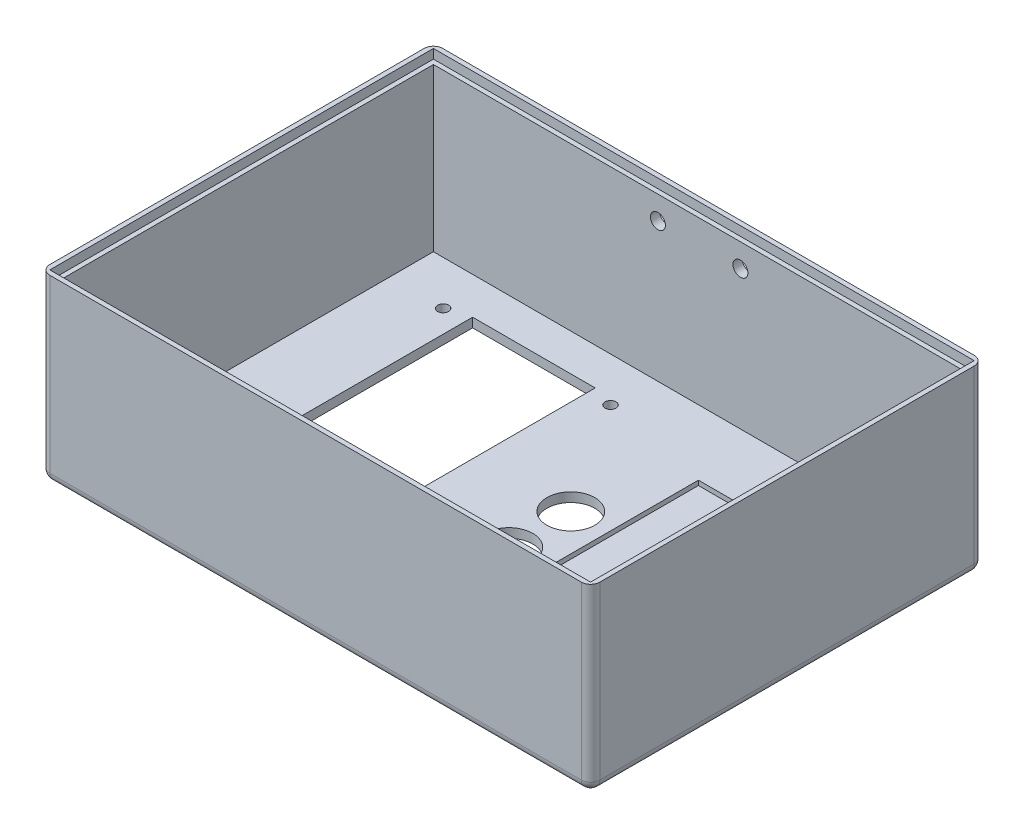
SolidWorks part; units mm, degrees
ref_plane "Front Plane" through (0, 0, 0) normal (0, 0, 1) x (1, 0, 0)
ref_plane "Top Plane" through (0, 0, 0) normal (0, 1, 0) x (1, 0, 0)
ref_plane "Right Plane" through (0, 0, 0) normal (1, 0, 0) x (0, 0, -1)
ref_plane "Plane1" through (0, 58.42, 0) normal (0, 1, 0) x (1, 0, 0)
sketch "Sketch1" plane through (0, 58.42, 0) normal (0, 1, 0) x (1, 0, 0)
  line L0 (-88.9, -63.5) -> (88.9, -63.5)
  line L1 (88.9, -63.5) -> (88.9, 63.5)
  line L2 (88.9, 63.5) -> (-88.9, 63.5)
  line L3 (-88.9, 63.5) -> (-88.9, -63.5)
extrude "Boss-Extrude1" add sketch "Sketch1" against normal blind 58.42
sketch "Sketch2" plane through (0, 58.42, 0) normal (0, 1, 0) x (-1, 0, 0)
  line L0 (87.4, 62) -> (-87.4, 62)
  line L1 (-87.4, 62) -> (-87.4, -62)
  line L2 (-87.4, -62) -> (87.4, -62)
  line L3 (87.4, -62) -> (87.4, 62)
extrude "Cut-Extrude1" cut sketch "Sketch2" against normal blind 3
sketch "Sketch3" plane through (0, 55.42, 0) normal (0, 1, 0) x (-1, 0, 0)
  line L0 (85.9, 60.5) -> (-85.9, 60.5)
  line L1 (-85.9, 60.5) -> (-85.9, -60.5)
  line L2 (-85.9, -60.5) -> (85.9, -60.5)
  line L3 (85.9, -60.5) -> (85.9, 60.5)
extrude "Cut-Extrude2" cut sketch "Sketch3" against normal blind 52.42
sketch "Sketch4" plane through (0, 3, 0) normal (0, 1, 0) x (-1, 0, 0)
  line L0 (21.624, -48.514) -> (61.248, -48.514)
  line L1 (61.248, -48.514) -> (61.248, 48.514)
  line L2 (61.248, 48.514) -> (21.624, 48.514)
  line L3 (21.624, 48.514) -> (21.624, -48.514)
extrude "Cut-Extrude3" cut sketch "Sketch4" against normal through all
sketch "Sketch5" plane through (0, 3, 0) normal (0, 1, 0) x (-1, 0, 0)
  line L0 (-20.8712, 52.0517) -> (-79.2912, 52.0517)
  line L1 (-79.2912, 52.0517) -> (-79.2912, -39.3883)
  line L2 (-79.2912, -39.3883) -> (-20.8712, -39.3883)
  line L3 (-20.8712, -39.3883) -> (-20.8712, 52.0517)
extrude "Cut-Extrude4" cut sketch "Sketch5" against normal blind 1.5
hole_wizard "M13 Clearance Hole1" positions "Sketch7" profile "Sketch6" hole size "M13" standard "ANSI Metric"
sketch "Sketch7" plane through (0, 3, 0) normal (0, 1, 0) x (1, 0, 0)
  point P0 (8.9925, -10.0168)
  point P1 (8.9925, 10.0168)
sketch "Sketch6" plane through (8.9925, 3, 10.0168) normal (1, 0, 0) x (0, 0, 1)
  line L0 (0, 0) -> (0, 3)
  line L1 (0, 3) -> (7.747, 3)
  line L2 (7.747, 3) -> (7.747, 0)
  line L5 (7.747, 0) -> (0, 0)
  line L11 (0, -6.35) -> (0, 107.95) construction
  dimension "Thru Hole Dia." = 15.494
  dimension "Thru Hole Depth" = 3
hole_wizard "M3 Clearance Hole1" positions "Sketch9" profile "Sketch8" hole size "M3" standard "ANSI Metric"
sketch "Sketch9" plane through (0, 3, 0) normal (0, 1, 0) x (1, 0, 0)
  point P0 (-68.487, 46.228)
  point P1 (-68.487, -46.228)
  point P2 (-14.385, -46.228)
  point P3 (-14.385, 46.228)
sketch "Sketch8" plane through (-68.487, 3, -46.228) normal (1, 0, 0) x (0, 0, 1)
  line L0 (0, 0) -> (0, 3)
  line L1 (0, 3) -> (1.778, 3)
  line L2 (1.778, 3) -> (1.778, 0)
  line L5 (1.778, 0) -> (0, 0)
  line L11 (0, -6.35) -> (0, 107.95) construction
  dimension "Thru Hole Dia." = 3.556
  dimension "Thru Hole Depth" = 3
fillet "Fillet1" radius 3 8 edges at (-88.9, 29.21, -63.5) (-88.9, 29.21, 63.5) (-88.9, 0, 0) (88.9, 29.21, -63.5) (0, 0, -63.5) (0, 0, 63.5) (88.9, 0, 0) (88.9, 29.21, 63.5)
sketch "Sketch10" plane through (0, 0, -63.5) normal (0, 0, -1) x (-1, 0, 0)
  line L5 (-19.05, 58.42) -> (19.05, 58.42)
  circle A0 centre (-13.335, 47.879) radius 2.413
  circle A1 centre (13.335, 47.879) radius 2.413
  point P5 (0, 0)
  dimension "D5" = 4.826
extrude "Cut-Extrude5" cut sketch "Sketch10" against normal up to surface (3 mm away) contours A0 | A1 up to face at (0, 29.21, -60.5)
